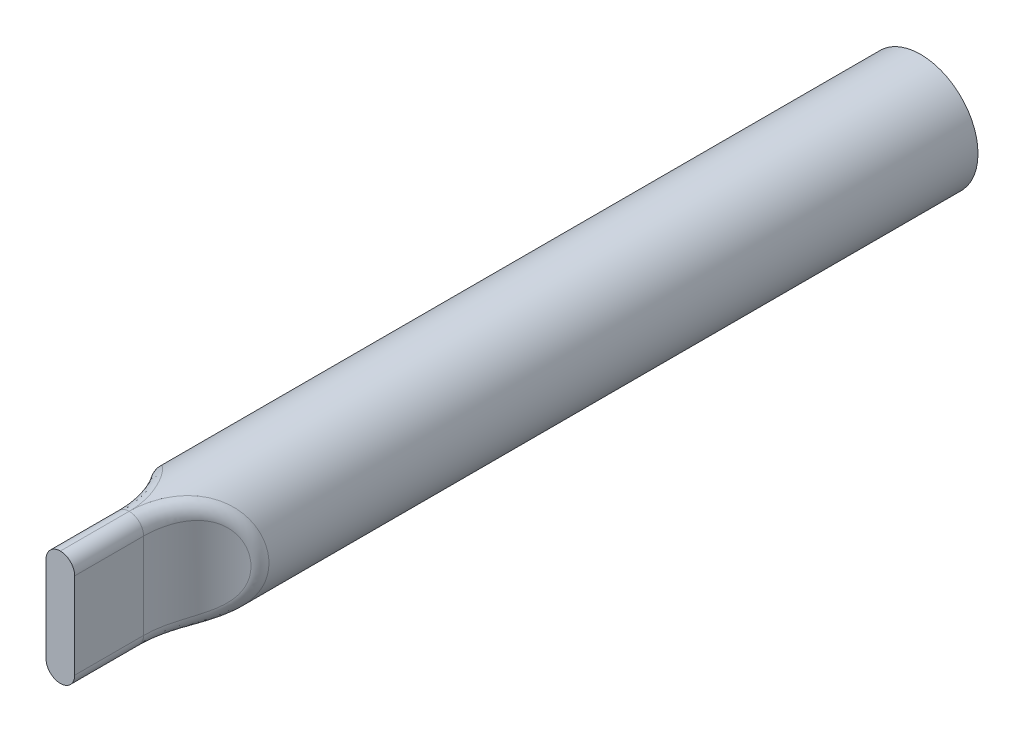
SolidWorks part; units mm, degrees
ref_plane "Front Plane" through (0, 0, 0) normal (0, 0, 1) x (1, 0, 0)
ref_plane "Top Plane" through (0, 0, 0) normal (0, 1, 0) x (1, 0, 0)
ref_plane "Right Plane" through (0, 0, 0) normal (1, 0, 0) x (0, 0, -1)
sketch "Sketch1" plane through (0, 0, 0) normal (0, 0, 1) x (1, 0, 0)
  circle A0 centre (0, 0) radius 2
  dimension "D1" = 4
extrude "Boss-Extrude1" add sketch "Sketch1" along normal blind 30
sketch "Sketch2" plane through (0, 0, 0) normal (0, 1, 0) x (1, 0, 0)
  line L0 (0, -30) -> (0, -25.1492) construction
  line L1 (-2, -30) -> (2, -30) construction
  line L2 (-0.5, -30) -> (-0.5, -27.5981)
  line L3 (-2, 0) -> (-2, -30) construction
  line L4 (-2, -25) -> (-2, -30)
  line L5 (-2, -30) -> (-0.5, -30)
  line L6 (2, -30) -> (0.5, -30)
  line L7 (2, -25) -> (2, -30)
  line L8 (0.5, -30) -> (0.5, -27.5981)
  arc A0 (-0.5, -27.5981) -> (-2, -25) centre (-3.5, -27.5981) ccw
  arc A1 (0.5, -27.5981) -> (2, -25) centre (3.5, -27.5981) cw
  point P11 (-0.5753, -29.9438)
  dimension "D2" = 3
  dimension "D1" = 1
  dimension "D3" = 5
extrude "Cut-Extrude1" cut sketch "Sketch2" against normal through all both and the other way through all
fillet "Fillet1" radius 0.5 6 edges at (0.5, -1.9365, 28.799) (1.9982, -0.0842, 25.001) (-0.5, -1.9365, 28.799) (-0.5, 1.9365, 28.799) (0.5, 1.9365, 28.799) (-1.9982, 0.0842, 25.001)
shell "Shell1" thickness 0.25 removed face at (2, 0, 0)
sketch "Sketch3" plane through (0, 0, 0) normal (0, 1, 0) x (1, 0, 0)
  line L0 (0, 0) -> (0, -9) construction
  line L1 (0, -9) -> (0, -14) construction
  line L2 (0, -14) -> (0, -19) construction
  circle A0 centre (0, -19) radius 1
  circle A1 centre (0, -14) radius 1
  circle A2 centre (0, -9) radius 1
  dimension "D1" = 2
  dimension "D2" = 5
  dimension "D3" = 9
extrude "Cut-Extrude2" cut sketch "Sketch3" against normal blind 30
